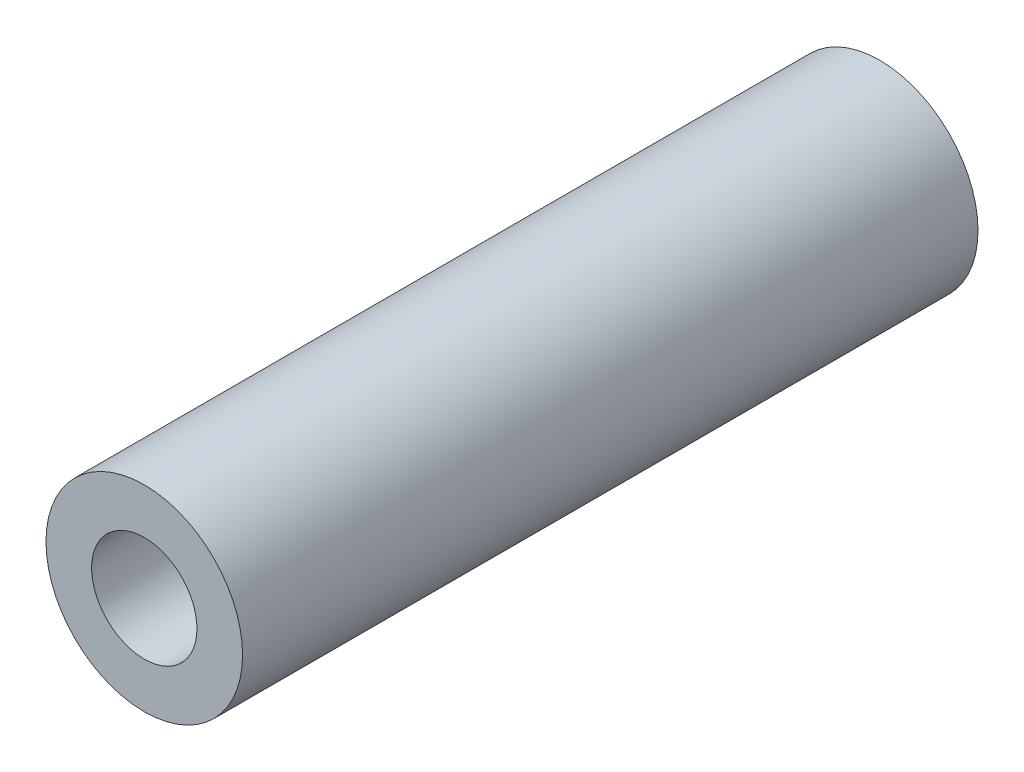
SolidWorks part; units mm, degrees
ref_plane "Front Plane" through (0, 0, 0) normal (0, 0, 1) x (1, 0, 0)
ref_plane "Top Plane" through (0, 0, 0) normal (0, 1, 0) x (1, 0, 0)
ref_plane "Right Plane" through (0, 0, 0) normal (1, 0, 0) x (0, 0, -1)
sketch "Sketch1" plane through (0, 0, 0) normal (0, 0, 1) x (1, 0, 0)
  circle A0 centre (0, 0) radius 4.7625
  circle A1 centre (0, 0) radius 2.5527
  dimension "D1" = 5.1054
  dimension "D2" = 9.525
extrude "Boss-Extrude1" add sketch "Sketch1" along normal mid plane 35.6375 contours A0 A1 region at (-4.6278, 0, 0)
